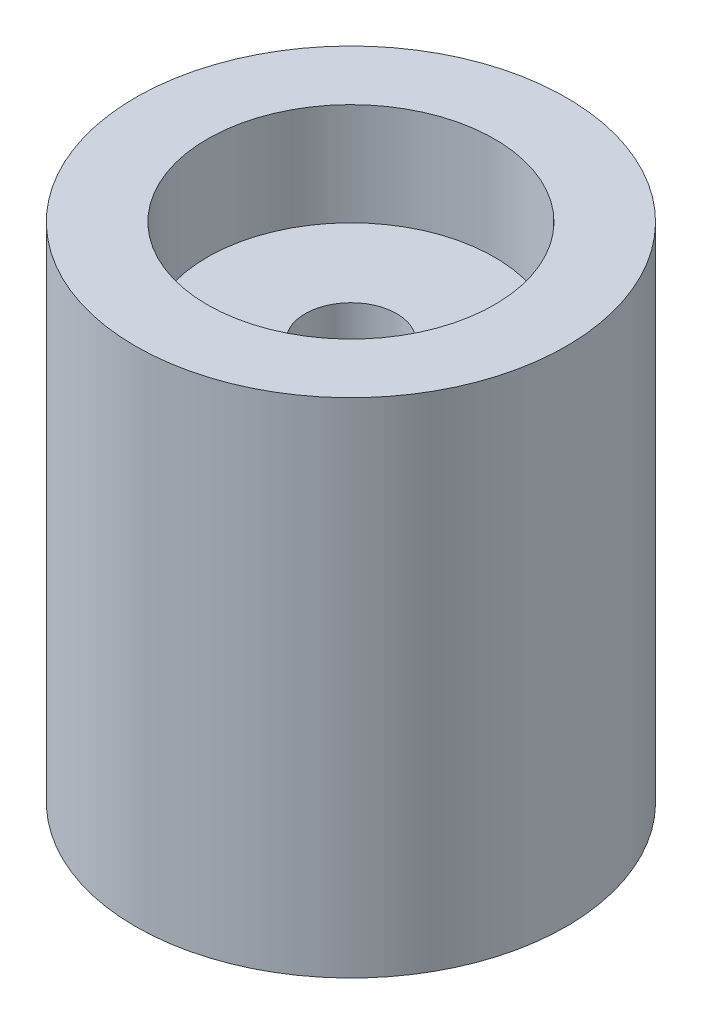
SolidWorks part; units mm, degrees
material "ABS"
ref_plane "前视基准面" through (0, 0, 0) normal (0, 0, 1) x (1, 0, 0)
ref_plane "上视基准面" through (0, 0, 0) normal (0, 1, 0) x (1, 0, 0)
ref_plane "右视基准面" through (0, 0, 0) normal (1, 0, 0) x (0, 0, -1)
other "Configuration Table"
sketch "草图1" plane through (0, 0, 0) normal (0, 1, 0) x (1, 0, 0)
  circle A1 centre (0, 0) radius 6
  dimension "D2" = 12
extrude "凸台-拉伸1" add sketch "草图1" along normal blind 14
sketch "草图2" plane through (0, 0, 0) normal (0, 1, 0) x (1, 0, 0)
  circle A0 centre (0, 0) radius 2.275
  dimension "D1" = 4.55
extrude "切除-拉伸1" cut sketch "草图2" along normal blind 3.9 contours A0
hole_wizard "M2.5 六角头螺栓的柱形沉头孔1" positions "草图3" profile "草图4" counterbore size "M2.5" standard "GB" end condition up to next
sketch "草图3" plane through (0, 14, 0) normal (0, 1, 0) x (1, 0, 0)
  point P0 (0, 0)
sketch "草图4" plane through (0, 14, 0) normal (1, 0, 0) x (0, 0, 1)
  line L0 (0, 0) -> (0, 10.1)
  line L1 (0, 10.1) -> (1.275, 10.1)
  line L3 (1.275, 10.1) -> (1.275, 2.85)
  line L4 (1.275, 2.85) -> (4, 2.85)
  line L5 (4, 2.85) -> (4, 0)
  line L7 (4, 0) -> (0, 0)
  line L11 (0, -6.35) -> (0, 107.95) construction
  dimension "通孔孔直径" = 2.55
  dimension "通孔孔深度" = 10.1
  dimension "柱形沉头孔直径" = 8
